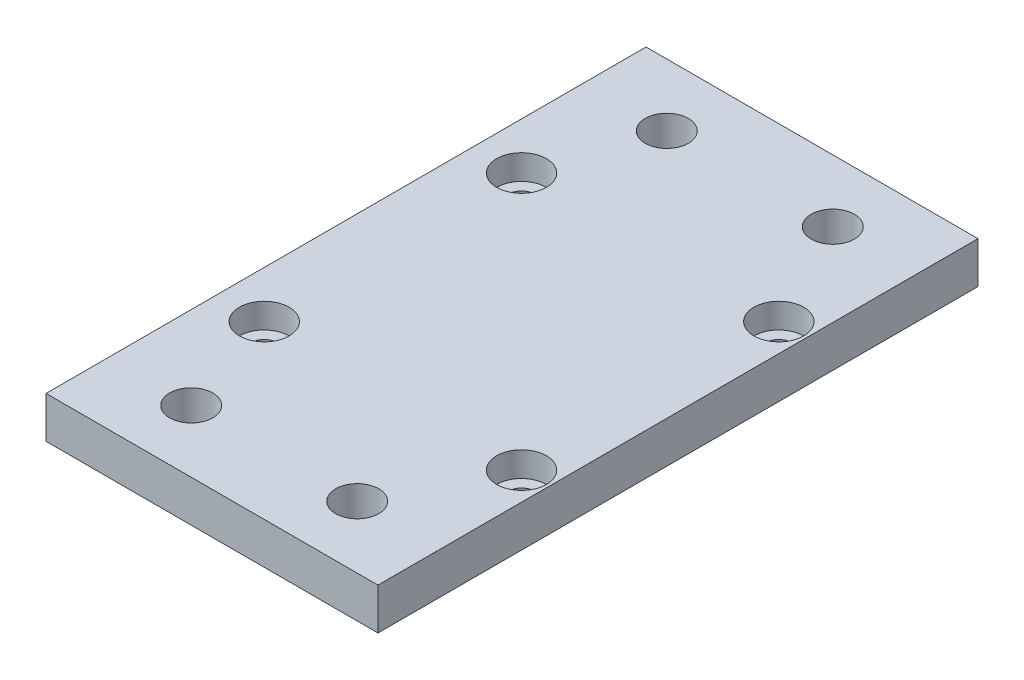
SolidWorks part; units mm, degrees
material "PET"
ref_plane "Front Plane" through (0, 0, 0) normal (0, 0, 1) x (1, 0, 0)
ref_plane "Top Plane" through (0, 0, 0) normal (0, 1, 0) x (1, 0, 0)
ref_plane "Right Plane" through (0, 0, 0) normal (1, 0, 0) x (0, 0, -1)
sketch "Sketch2" plane through (0, 0, 0) normal (0, 1, 0) x (1, 0, 0)
  line L0 (-21.15, 21.15) -> (21.15, -21.15) construction
  line L1 (-21.15, -21.15) -> (21.15, -21.15)
  line L2 (-21.15, -21.15) -> (-21.15, 21.15)
  line L3 (-21.15, 21.15) -> (21.15, 21.15)
  line L4 (21.15, -21.15) -> (21.15, 21.15)
  line L5 (-21.15, 21.15) -> (21.15, 21.15)
  line L6 (-21.15, 21.15) -> (-21.15, 36.15)
  line L7 (-21.15, 36.15) -> (21.15, 36.15)
  line L8 (21.15, 21.15) -> (21.15, 36.15)
  line L9 (21.15, -21.15) -> (-21.15, -21.15)
  line L10 (21.15, -21.15) -> (21.15, -36.15)
  line L11 (21.15, -36.15) -> (-21.15, -36.15)
  line L12 (-21.15, -21.15) -> (-21.15, -36.15)
  line L13 (-21.15, 28.65) -> (21.15, 28.65) construction
  line L14 (-21.15, -28.65) -> (21.15, -28.65) construction
  line L15 (15.5, 15.5) -> (-15.5, -15.5) construction
  circle A0 centre (-11.15, 28.65) radius 2.6
  circle A1 centre (8.85, 28.65) radius 2.6
  circle A2 centre (-11.15, -28.65) radius 2.6
  circle A3 centre (8.85, -28.65) radius 2.6
  circle A4 centre (-15.5, 15.5) radius 1.6
  circle A5 centre (15.5, -15.5) radius 1.6
  circle A6 centre (15.5, 15.5) radius 1.6
  circle A7 centre (-15.5, -15.5) radius 1.6
  dimension "D3" = 5.2
  dimension "D4" = 5.2
  dimension "D9" = 5.2
  dimension "D10" = 5.2
  dimension "D13" = 3.2
  dimension "D14" = 3.2
  dimension "D15" = 3.2
  dimension "D16" = 3.2
  dimension "D1" = 42.3
  dimension "D2" = 42.3
  dimension "D5" = 15
  dimension "D6" = 15
  dimension "D7" = 20
  dimension "D8" = 12.3
  dimension "D11" = 20
  dimension "D12" = 12.3
  dimension "D17" = 31
  dimension "D18" = 10
extrude "Boss-Extrude1" add sketch "Sketch2" along normal blind 5 contours L1 L4 L3 L2 A7 A6 A5 A4 | L1 L12 L11 L10 A3 A2 | L3 L8 L7 L6 A1 A0 region at (0, 0, 0) region at (0.0825, 0, 28.65) region at (0.0825, 0, -28.65)
sketch "Sketch3" plane through (0, 5, 0) normal (0, 1, 0) x (1, 0, 0)
  circle A0 centre (-15.5, 15.5) radius 3
  circle A1 centre (15.5, 15.5) radius 3
  circle A2 centre (15.5, -15.5) radius 3
  circle A3 centre (-15.5, -15.5) radius 3
  dimension "D1" = 6
  dimension "D2" = 6
  dimension "D3" = 6
  dimension "D4" = 6
extrude "Cut-Extrude1" cut sketch "Sketch3" against normal blind 3
sketch "Sketch5" plane through (0, 0, 0) normal (0, -1, 0) x (1, 0, 0)
  line L0 (21.15, 36.15) -> (-21.15, 36.15) construction
  line L1 (21.15, -36.15) -> (18.85, -36.15)
  line L2 (21.15, -36.15) -> (21.15, 36.15)
  line L3 (21.15, 36.15) -> (18.85, 36.15)
  line L4 (18.85, -36.15) -> (18.85, 36.15)
  dimension "D1" = 2.3
extrude "Cut-Extrude2" cut sketch "Sketch5" against normal through all
